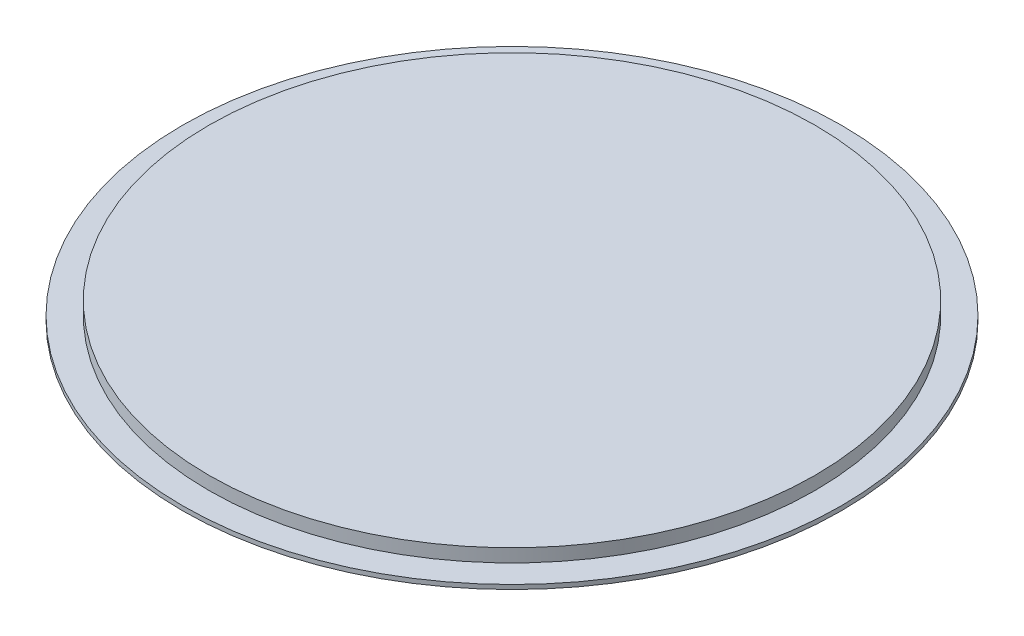
SolidWorks part; units mm, degrees
ref_plane "Front Plane" through (0, 0, 0) normal (0, 0, 1) x (1, 0, 0)
ref_plane "Top Plane" through (0, 0, 0) normal (0, 1, 0) x (1, 0, 0)
ref_plane "Right Plane" through (0, 0, 0) normal (1, 0, 0) x (0, 0, -1)
sketch "Sketch1" plane through (0, 0, 0) normal (0, 1, 0) x (1, 0, 0)
  circle A0 centre (0, 0) radius 37.5
  dimension "D1" = 75
extrude "Boss-Extrude1" add sketch "Sketch1" along normal blind 1
sketch "Sketch2" plane through (0, 0, 0) normal (0, 1, 0) x (1, 0, 0)
  circle A0 centre (0, 0) radius 34.5
  dimension "D1" = 69
extrude "Boss-Extrude2" add sketch "Sketch2" along normal blind 3
fillet "Fillet1" radius 5 1 edges at (0, 0, 37.5)
sketch "Sketch3" plane through (0, 1, 0) normal (0, 1, 0) x (1, 0, 0)
  line L0 (0, 0) -> (0, 37.5) construction
  circle A1 centre (0, 0) radius 37.5 construction
  circle A2 centre (0, 0) radius 37.5
extrude "Boss-Extrude3" add sketch "Sketch3" along normal blind 0.5
